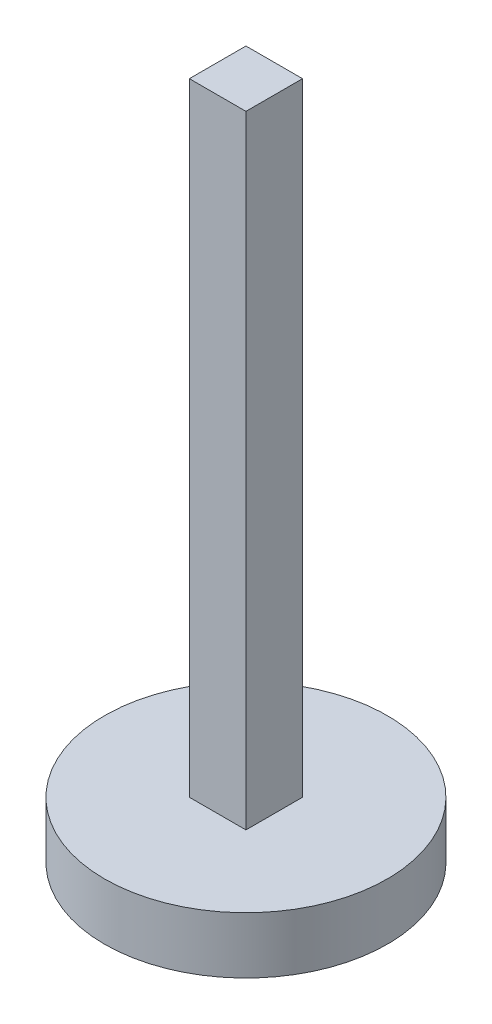
SolidWorks part; units mm, degrees
ref_plane "Front Plane" through (0, 0, 0) normal (0, 0, 1) x (1, 0, 0)
ref_plane "Top Plane" through (0, 0, 0) normal (0, 1, 0) x (1, 0, 0)
ref_plane "Right Plane" through (0, 0, 0) normal (1, 0, 0) x (0, 0, -1)
sketch "Sketch1" plane through (0, 0, 0) normal (0, 1, 0) x (1, 0, 0)
  line L1 (-10, -10) -> (10, -10)
  line L2 (-10, -10) -> (-10, 10)
  line L3 (-10, 10) -> (10, 10)
  line L4 (10, -10) -> (10, 10)
  line L5 (-10, -10) -> (10, 10) construction
  line L6 (-10, 10) -> (10, -10) construction
  circle A0 centre (0, 0) radius 50
  dimension "D1" = 100
  dimension "D2" = 20
  dimension "D3" = 20
extrude "Boss-Extrude1" add sketch "Sketch1" along normal blind 20
extrude "Boss-Extrude2" add sketch "Sketch1<2>" along normal blind 240 contours L1 L4 L3 L2 region at (0, 0, 0)
sketch "Sketch1<2>" plane through (0, 0, 0) normal (0, 1, 0) x (1, 0, 0) same geometry as "Sketch1"
